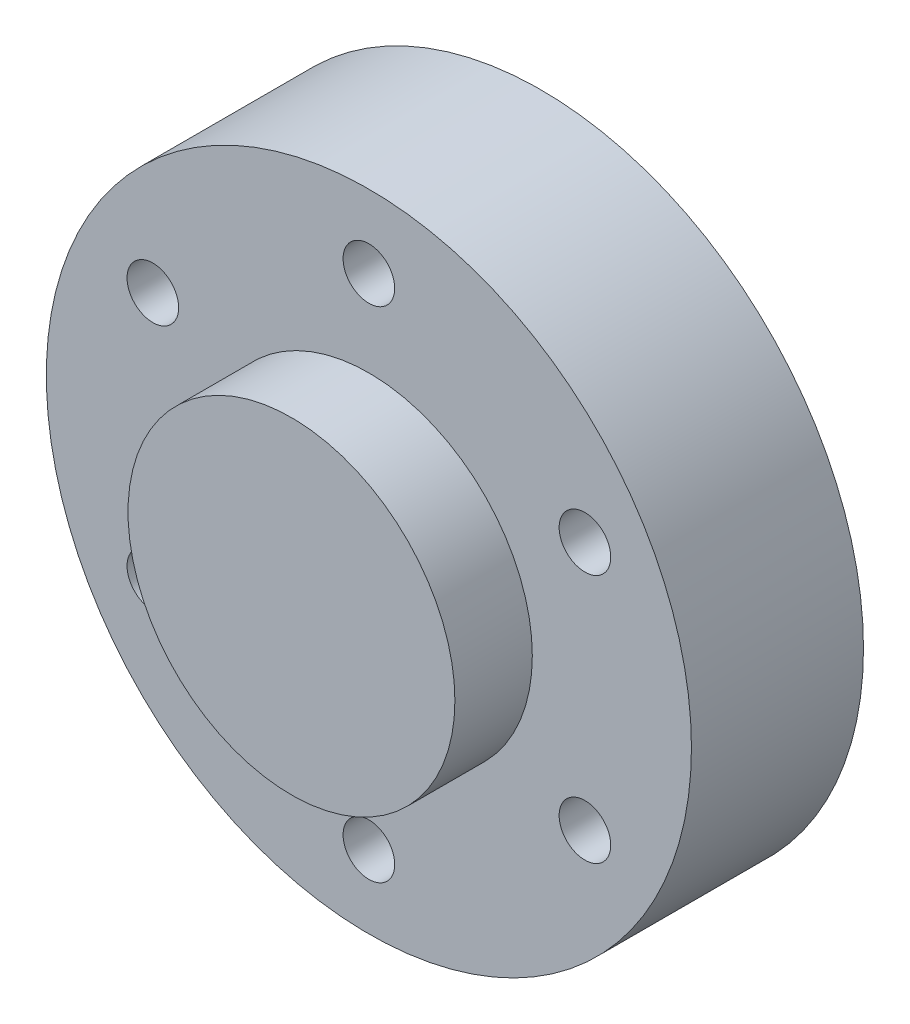
SolidWorks part; units mm, degrees
ref_plane "Front Plane" through (0, 0, 0) normal (0, 0, 1) x (1, 0, 0)
ref_plane "Top Plane" through (0, 0, 0) normal (0, 1, 0) x (1, 0, 0)
ref_plane "Right Plane" through (0, 0, 0) normal (1, 0, 0) x (0, 0, -1)
sketch "Sketch2" plane through (0, 0, 0) normal (0, 0, 1) x (1, 0, 0)
  circle A0 centre (0, 0) radius 9.5
  circle A1 centre (0, 0) radius 14.5 construction
  circle A3 centre (0, 0) radius 18.75
  circle A4 centre (0, 14.5) radius 1.5
  circle A5 centre (12.5574, 7.25) radius 1.5
  circle A6 centre (12.5574, -7.25) radius 1.5
  circle A7 centre (0, -14.5) radius 1.5
  circle A8 centre (-12.5574, -7.25) radius 1.5
  circle A9 centre (-12.5574, 7.25) radius 1.5
  point P21 (0, 0)
  dimension "D1" = 19
  dimension "D3" = 29
  dimension "D4" = 37.5
  dimension "D5" = 3
  dimension "D6" = 6
extrude "Boss-Extrude1" add sketch "Sketch2" along normal blind 10 contours A3 A9 A8 A7 A6 A5 A4 A0 | A0 region at (0, 0, 0) region at (-18.2197, 0, 0)
sketch "Sketch3" plane through (0, 0, 10) normal (0, 0, 1) x (1, 0, 0)
  circle A0 centre (0, 0) radius 9.5
  dimension "D1" = 19
extrude "Boss-Extrude2" add sketch "Sketch3" along normal blind 4.5
sketch "Sketch6" plane through (0, 0, 0) normal (0, 0, -1) x (-1, 0, 0)
  circle A0 centre (0, 0) radius 9.5
  dimension "D1" = 19
extrude "Boss-Extrude4" add sketch "Sketch6" along normal blind 4.5 contours A0
sketch "Sketch7" plane through (0, 0, -4.5) normal (0, 0, -1) x (-1, 0, 0)
  circle A0 centre (0, 0) radius 1.525
  dimension "D1" = 3.05
extrude "Boss-Extrude5" add sketch "Sketch7" along normal blind 1
fillet "Fillet2" radius 0.05 1 edges at (-1.525, 0, -5.5)
sketch "Sketch9" plane through (0, 0, -5.5) normal (0, 0, -1) x (-1, 0, 0)
  circle A0 centre (0, 0) radius 1.4
  dimension "D1" = 2.8
extrude "Cut-Extrude1" cut sketch "Sketch9" against normal blind 10
